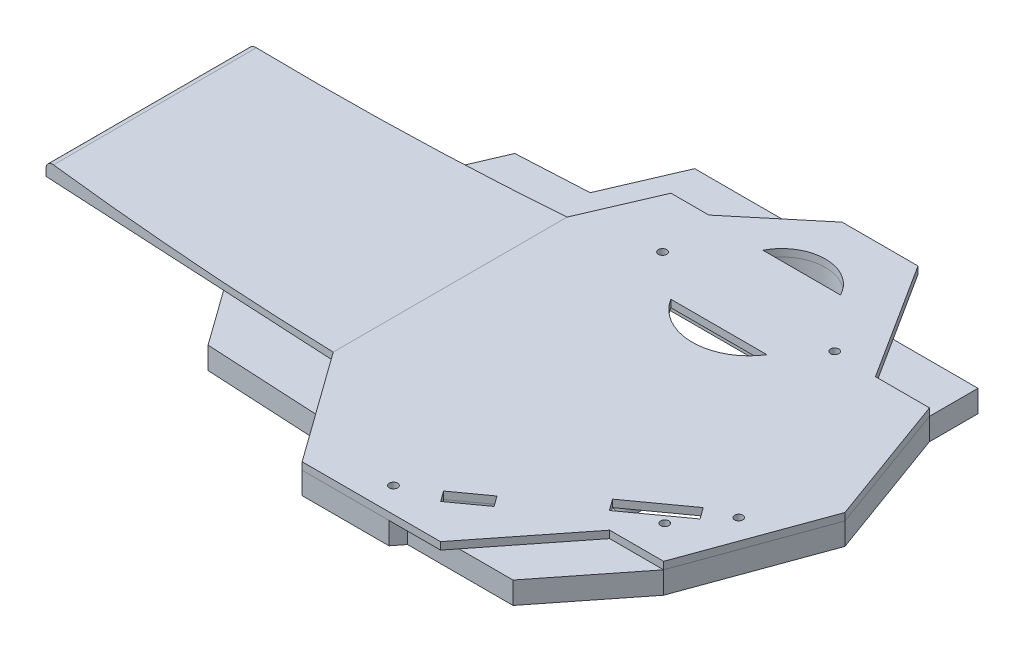
SolidWorks part; units mm, degrees
ref_plane "前视基准面" through (0, 0, 0) normal (0, 0, 1) x (1, 0, 0)
ref_plane "上视基准面" through (0, 0, 0) normal (0, 1, 0) x (1, 0, 0)
ref_plane "右视基准面" through (0, 0, 0) normal (1, 0, 0) x (0, 0, -1)
other "Configuration Table"
sketch "草图2" plane through (0, 0, 0) normal (0, 1, 0) x (1, 0, 0)
  line L0 (0, 0) -> (243.6421, 0) construction
  line L30 (176.8295, 36.1855) -> (82.5273, -31.8251) construction
  line L35 (141.8216, 68.0827) -> (121.1619, 68.0827)
  line L36 (176.8295, 36.1855) -> (190, 0)
  line L37 (104.1466, -61.9173) -> (82.5273, -31.8251)
  line L38 (82.5273, -31.8251) -> (0, -27.5)
  line L39 (0, -27.5) -> (0, 27.5)
  line L40 (0, 27.5) -> (82.5273, 31.8251)
  line L43 (190, 0) -> (176.8295, -36.1855)
  line L45 (82.5273, 31.8251) -> (91.0398, 51.6089)
  line L51 (104.1466, -61.9173) -> (190, 0) construction
  line L53 (141.8216, -61.9173) -> (104.1466, -61.9173)
  line L55 (82.5273, 31.8251) -> (342.4089, 31.8251) construction
  line L57 (176.8295, 36.1855) -> (176.8295, 0) construction
  line L58 (176.8295, 0) -> (176.8295, -36.1855) construction
  line L59 (82.5273, -31.8251) -> (342.4089, -31.8251) construction
  line L62 (91.0398, 51.6089) -> (101.351, 51.6089)
  line L63 (101.351, 51.6089) -> (121.1619, 68.0827)
  line L64 (141.8216, 68.0827) -> (162.1337, 36.1855)
  line L65 (162.1337, 36.1855) -> (176.8295, 36.1855)
  line L66 (176.8295, -36.1855) -> (162.1337, -36.1855)
  line L67 (162.1337, -36.1855) -> (141.8216, -61.9173)
  dimension "D1" = 190
  dimension "D2" = 130
  dimension "D4" = 55
  dimension "D6" = 93
  dimension "D7" = 93
  dimension "D8" = 140
extrude "凸台-拉伸1" add sketch "草图2" along normal blind 2
sketch "草图6" plane through (0, 2, 0) normal (0, 1, 0) x (1, 0, 0)
  line L0 (82.5273, 31.8251) -> (82.5273, -31.8251)
  line L1 (82.5273, -31.8251) -> (0, -27.5)
  line L2 (0, -27.5) -> (0, 27.5)
  line L3 (0, 27.5) -> (82.5273, 31.8251)
extrude "凸台-拉伸2" add sketch "草图6" along normal blind 2
sketch "草图7" plane through (0, 0, 0) normal (0, 0, 1) x (1, 0, 0)
  line L2 (82.5273, 2) -> (82.5273, 30.7408)
  line L3 (82.5273, 30.7408) -> (0, 4)
  spline S0 degree 2 poles (82.5273, 2) (41.2153, 1.0012) (0, 4) knots 0 0 0 1 1 1
extrude "切除-拉伸3" cut sketch "草图7" against normal through all both and the other way through all
fillet "圆角1" radius 2 1 edges at (0, 4, 0)
ref_plane "基准面3" through (0, -12, 0) normal (0, -1, 0) x (-1, 0, 0)
sketch "草图10" plane through (0, 0, 0) normal (0, -1, 0) x (1, 0, 0)
  line L0 (0, 27.5) -> (82.5273, 31.8251)
  line L1 (82.5273, 31.8251) -> (171.8529, 31.8251)
  line L2 (171.8529, 31.8251) -> (171.8529, -31.8251)
  line L3 (171.8529, -31.8251) -> (82.5273, -31.8251)
  line L4 (82.5273, -31.8251) -> (0, -27.5)
  line L5 (0, -27.5) -> (0, 27.5)
sketch "飞机跑道" plane through (0, 2, 0) normal (0, 1, 0) x (1, 0, 0)
  line L0 (176.8295, 36.1855) -> (82.5273, -31.8251)
  line L1 (190, 0) -> (104.1466, -61.9173)
  line L2 (183.4148, 18.0928) -> (93.337, -46.8712) construction
  line L3 (190, 0) -> (176.8295, 36.1855) construction
  line L4 (82.5273, -31.8251) -> (104.1466, -61.9173) construction
sketch "草图13" plane through (0, 0, 0) normal (0, -1, 0) x (1, 0, 0)
  line L0 (53.5015, -30.3039) -> (58.4123, -41.717)
  line L1 (82.5273, -31.8251) -> (0, -27.5) construction
  line L2 (58.4123, -41.717) -> (77.9269, -42.7397)
  line L3 (77.9269, -42.7397) -> (86.4844, -62.6282)
  line L4 (86.4844, -62.6282) -> (136.1647, -62.6282)
  line L5 (176.8295, 36.1855) -> (190, 0)
  line L6 (190, 0) -> (176.8295, -36.1855)
  line L7 (136.1647, -62.6282) -> (144.5841, -49.4069)
  line L8 (144.5841, -49.4069) -> (176.8295, -49.4069)
  line L9 (176.8295, -49.4069) -> (176.8295, -36.1855)
  line L11 (176.8295, 36.1855) -> (158.7432, 59.0976)
  line L12 (158.7432, 59.0976) -> (130.0164, 59.0976)
  line L13 (130.0164, 59.0976) -> (127.7906, 61.9173)
  line L14 (104.1466, 61.9173) -> (141.8216, 61.9173) construction
  line L15 (127.7906, 61.9173) -> (104.1466, 61.9173)
  line L16 (104.1466, 61.9173) -> (93.337, 46.8712)
  line L17 (93.337, 46.8712) -> (61.8459, 45.2208)
  line L18 (61.8459, 45.2208) -> (51.0363, 30.1747)
  line L19 (0, 27.5) -> (82.5273, 31.8251) construction
  line L21 (171.8529, 31.8251) -> (171.8529, -31.8251)
  line L25 (53.5015, -30.3039) -> (82.5273, -31.8251)
  line L26 (82.5273, -31.8251) -> (171.8529, -31.8251)
  line L27 (51.0363, 30.1747) -> (82.5273, 31.8251)
  line L28 (82.5273, 31.8251) -> (171.8529, 31.8251)
extrude "凸台-拉伸4" add sketch "草图13" along normal blind 6 separate body contours L18 L27 L28 L21 L26 L25 L0 L2 L3 L4 L7 L8 L9 L6 L5 L11 L12 L13 L15 L16 L17
sketch "草图17" plane through (0, 2, 0) normal (0, 1, 0) x (1, 0, 0)
  line L3 (116.0112, 26.5953) -> (142.1812, 26.5953)
  line L4 (138.1274, 50.6813) -> (116.9896, 50.6813)
  arc A1 (116.0112, 26.5953) -> (142.1812, 26.5953) centre (129.0962, 34.7996) ccw
  arc A2 (116.9896, 50.6813) -> (138.1274, 50.6813) centre (127.5585, 45.2443) cw
sketch "草图18" plane through (0, 2, 0) normal (0, 1, 0) x (1, 0, 0)
  line L4 (169.5639, -18.1259) -> (155.2183, -28.4719)
  line L5 (171.8094, -21.2395) -> (169.5639, -18.1259)
  line L6 (157.4639, -31.5855) -> (171.8094, -21.2395)
  line L7 (155.2183, -28.4719) -> (157.4639, -31.5855)
  line L8 (169.5639, -18.1259) -> (155.2183, -28.4719)
  line L9 (171.8094, -21.2395) -> (169.5639, -18.1259)
  line L10 (157.4639, -31.5855) -> (171.8094, -21.2395)
  line L11 (155.2183, -28.4719) -> (157.4639, -31.5855)
  line L12 (130.3021, -49.5646) -> (132.3616, -52.4203)
  line L13 (132.3616, -52.4203) -> (140.8147, -46.3239)
  line L14 (140.8147, -46.3239) -> (138.7552, -43.4683)
  line L15 (138.7552, -43.4683) -> (130.3021, -49.5646)
  line L16 (130.3021, -49.5646) -> (132.3616, -52.4203)
  line L17 (132.3616, -52.4203) -> (140.8147, -46.3239)
  line L18 (140.8147, -46.3239) -> (138.7552, -43.4683)
  line L19 (138.7552, -43.4683) -> (130.3021, -49.5646)
  dimension "D1" = 0
  dimension "D2" = 0
extrude "切除-拉伸7" cut sketch "草图18" against normal through all
sketch "草图19" plane through (0, 2, 0) normal (0, 1, 0) x (1, 0, 0)
  line L0 (82.5273, -31.8251) -> (176.8295, 36.1855)
  line L1 (176.8295, 36.1855) -> (190, 0)
  line L2 (190, 0) -> (104.1466, -61.9173)
  line L3 (104.1466, -61.9173) -> (82.5273, -31.8251)
ref_plane "基准面4" through (40.2637, -40.2637, 0) normal (-0.7071, 0.7071, 0) x (0, 0, -1)
sketch "草图23" plane through (40.2637, -40.2637, 0) normal (-0.7071, 0.7071, 0) x (0, 0, -1)
  line L0 (-9.292, -59.7699) -> (13.6381, -59.7699)
  line L1 (-31.8251, -59.7699) -> (31.8251, -59.7699) construction
  line L2 (13.6381, -59.7699) -> (13.6381, -71.5206)
  line L3 (13.6381, -71.5206) -> (-9.292, -71.5206)
  line L4 (-9.292, -71.5206) -> (-9.292, -60.8098)
  line L5 (-9.292, -60.8098) -> (-9.292, -59.7699)
extrude "凸台-拉伸5" [suppressed] add sketch "草图23" along normal blind 2 draft 45 separate body draft outward yes
sketch "草图24" plane through (0, 2, 0) normal (0, 1, 0) x (1, 0, 0)
  circle A0 centre (85.4903, 11.0478) radius 1.6973
  circle A1 centre (85.4903, -6.5413) radius 1.5
extrude "凸台-拉伸11" [suppressed] add sketch "草图24" along normal up to surface (2.9629 mm away) separate body contours A0 | A1
ref_plane "基准面6" through (0, 4, 0) normal (0, 1, 0) x (1, 0, 0)
sketch "草图25" plane through (0, 4, 0) normal (0, 1, 0) x (1, 0, 0)
  line L1 (67.0613, -53.2409) -> (67.0613, 49.4655) construction
  line L2 (-9.3986, 0) -> (224.1358, 0) construction
  circle A0 centre (67.0613, -25.5664) radius 3
  circle A1 centre (67.0613, 25.5664) radius 3
  circle A3 centre (168.0155, -27.0476) radius 1
  circle A4 centre (150.7888, 25.9399) radius 3
  circle A5 centre (150.7888, -25.9399) radius 3
  point P14 (168.0155, -27.0476)
extrude "切除-拉伸8" cut sketch "草图17" against normal through all contours L4 A2 | L4 A2 | A1 L3 | A1 L3 region at (129.0962, 2, -23.6319) region at (127.5585, 2, -53.332)
hole_wizard "#4-40 螺纹孔3" positions "草图25" profile "草图26" tap size "#4-40" standard "ANSI Inch" end condition through all
sketch "草图26" plane through (168.0155, 4, 27.0476) normal (1, 0, 0) x (0, 0, 1)
  line L0 (0, 0) -> (0, 10)
  line L1 (0, 10) -> (1.1303, 10)
  line L2 (1.1303, 10) -> (1.1303, 0)
  line L5 (1.1303, 0) -> (0, 0)
  line L11 (0, -6.35) -> (0, 107.95) construction
  dimension "通孔螺纹孔钻头直径" = 2.2606
  dimension "通孔螺纹孔钻头深度" = 10
cosmetic thread "孔螺纹线4" parameters "D2"=2.8448
sketch "草图29" plane through (0, 0, 0) normal (0, -1, 0) x (1, 0, 0)
  circle A5 centre (85.1794, -19.7075) radius 3.1
  circle A6 centre (85.1794, -19.7075) radius 3.1
  circle A7 centre (150.7888, -19.7075) radius 3.1
  circle A8 centre (150.7888, -19.7075) radius 3.1
  circle A9 centre (150.7888, 19.7075) radius 3.1
  circle A10 centre (150.7888, 19.7075) radius 3.1
  circle A11 centre (85.1794, 19.7075) radius 3.1
  circle A12 centre (85.1794, 19.7075) radius 3.1
  dimension "D1" = 0
  dimension "D2" = 0
  dimension "D3" = 0
  dimension "D4" = 0
extrude "凸台-拉伸14" add sketch "草图29" along normal blind 6 contours A6 | A8 | A10 | A12 region at (85.1794, 0, -19.7075) region at (150.7888, 0, -19.7075) region at (150.7888, 0, 19.7075)
sketch "草图33" plane through (0, 2, 0) normal (0, 1, 0) x (1, 0, 0)
  point P0 (150.6025, 36.6082)
  point P3 (103.7494, 36.6082)
hole_wizard "#4-40 螺纹孔4" positions "草图33" profile "草图32" tap size "#4-40" standard "ANSI Inch" end condition through all
sketch "草图32" plane through (150.6025, 2, -36.6082) normal (1, 0, 0) x (0, 0, 1)
  line L0 (0, 0) -> (0, 8)
  line L1 (0, 8) -> (1.1303, 8)
  line L2 (1.1303, 8) -> (1.1303, 0)
  line L5 (1.1303, 0) -> (0, 0)
  line L11 (0, -6.35) -> (0, 107.95) construction
  dimension "通孔螺纹孔钻头直径" = 2.2606
  dimension "通孔螺纹孔钻头深度" = 8
cosmetic thread "孔螺纹线8" parameters "D2"=2.8448
cosmetic thread "孔螺纹线9" parameters "D2"=2.8448
sketch "草图36" plane through (0, 2, 0) normal (0, 1, 0) x (1, 0, 0)
  point P0 (176.7356, -15.6397)
  point P3 (122.1817, -55.0926)
hole_wizard "#4-40 螺纹孔5" positions "草图36" profile "草图35" tap size "#4-40" standard "ANSI Inch" end condition through all
sketch "草图35" plane through (176.7356, 2, 15.6397) normal (1, 0, 0) x (0, 0, 1)
  line L0 (0, 0) -> (0, 8)
  line L1 (0, 8) -> (1.1303, 8)
  line L2 (1.1303, 8) -> (1.1303, 0)
  line L5 (1.1303, 0) -> (0, 0)
  line L11 (0, -6.35) -> (0, 107.95) construction
  dimension "通孔螺纹孔钻头直径" = 2.2606
  dimension "通孔螺纹孔钻头深度" = 8
cosmetic thread "孔螺纹线12" parameters "D2"=2.8448
cosmetic thread "孔螺纹线13" parameters "D2"=2.8448
